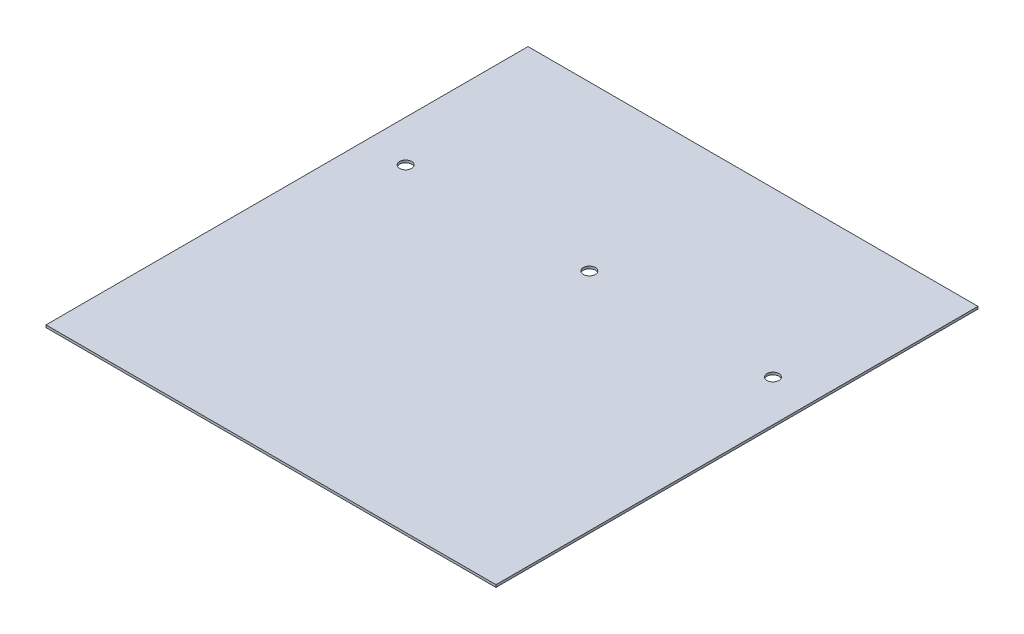
SolidWorks part; units mm, degrees
ref_plane "Front Plane" through (0, 0, 0) normal (0, 0, 1) x (1, 0, 0)
ref_plane "Top Plane" through (0, 0, 0) normal (0, 1, 0) x (1, 0, 0)
ref_plane "Right Plane" through (0, 0, 0) normal (1, 0, 0) x (0, 0, -1)
sketch "Sketch1" plane through (0, 0, 0) normal (0, 1, 0) x (1, 0, 0)
  line L0 (93.345, -199.9996) -> (93.345, -67.9196) construction
  line L1 (0, 0) -> (186.69, 0)
  line L2 (0, 0) -> (0, -199.9996)
  line L3 (0, -199.9996) -> (186.69, -199.9996)
  line L4 (186.69, 0) -> (186.69, -199.9996)
  line L5 (93.345, -67.9196) -> (186.69, -67.9196) construction
  line L6 (93.345, -67.9196) -> (0, -67.9196) construction
  circle A0 centre (93.345, -67.9196) radius 2.5
  circle A1 centre (17.145, -67.9196) radius 2.5
  circle A2 centre (93.345, -67.9196) radius 2.5
  circle A3 centre (169.545, -67.9196) radius 2.5
  dimension "D4" = 5
  dimension "D1" = 199.9996
  dimension "D2" = 186.69
  dimension "D3" = 132.08
  dimension "D5" = 2
  dimension "D6" = 2
extrude "Boss-Extrude1" add sketch "Sketch1" against normal blind 1 contours L4 L1 L2 L3 A3 A1 A0 region at (93.345, 0, 100.0505)
